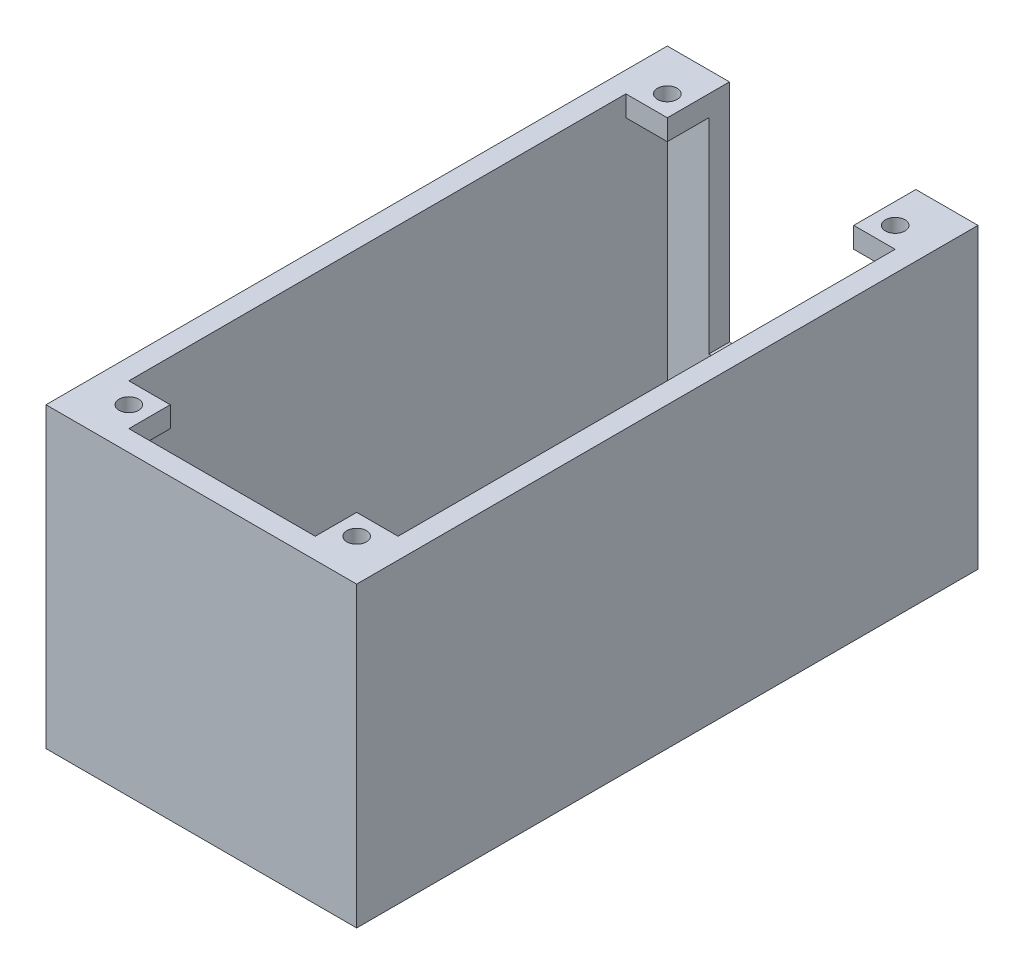
SolidWorks part; units mm, degrees
ref_plane "Front Plane" through (0, 0, 0) normal (0, 0, 1) x (1, 0, 0)
ref_plane "Top Plane" through (0, 0, 0) normal (0, 1, 0) x (1, 0, 0)
ref_plane "Right Plane" through (0, 0, 0) normal (1, 0, 0) x (0, 0, -1)
sketch "Sketch1" plane through (0, 0, 0) normal (0, 1, 0) x (1, 0, 0)
  line L1 (-19.05, -38.1) -> (19.05, -38.1)
  line L2 (-19.05, -38.1) -> (-19.05, 38.1)
  line L3 (-19.05, 38.1) -> (19.05, 38.1)
  line L4 (19.05, -38.1) -> (19.05, 38.1)
  line L5 (-19.05, -38.1) -> (19.05, 38.1) construction
  line L6 (-19.05, 38.1) -> (19.05, -38.1) construction
  point P0 (0, 0)
  dimension "D1" = 38.1
  dimension "D2" = 76.2
extrude "Boss-Extrude1" add sketch "Sketch1" along normal blind 2.54
hole_wizard "M2 Clearance Hole1 - to drone" positions "Sketch3" profile "Sketch4" hole size "M2" standard "ANSI Metric" end condition through all
sketch "Sketch3" plane through (0, 2.54, 0) normal (0, 1, 0) x (1, 0, 0)
  line L0 (-13.97, 0) -> (13.97, 0) construction
  point P0 (-13.97, 0)
  point P2 (13.97, 0)
  point P10 (0, 0)
  dimension "D1" = 27.94
sketch "Sketch4" plane through (-13.97, 2.54, 0) normal (1, 0, 0) x (0, 0, 1)
  line L0 (0, 0) -> (0, 2.54)
  line L1 (0, 2.54) -> (1.2, 2.54)
  line L2 (1.2, 2.54) -> (1.2, 0)
  line L5 (1.2, 0) -> (0, 0)
  line L11 (0, -6.35) -> (0, 107.95) construction
  dimension "Thru Hole Dia." = 2.4
  dimension "Thru Hole Depth" = 2.54
hole_wizard "M2 Clearance Hole2 - to Pi" positions "Sketch5" profile "Sketch6" hole size "M2" standard "ANSI Metric" end condition through all
sketch "Sketch5" plane through (0, 2.54, 0) normal (0, 1, 0) x (1, 0, 0)
  line L1 (-5.6998, -23.5001) -> (5.6998, -23.5001) construction
  line L2 (-5.6998, -23.5001) -> (-5.6998, 23.5001) construction
  line L3 (-5.6998, 23.5001) -> (5.6998, 23.5001) construction
  line L4 (5.6998, -23.5001) -> (5.6998, 23.5001) construction
  line L5 (-5.6998, -23.5001) -> (5.6998, 23.5001) construction
  line L6 (-5.6998, 23.5001) -> (5.6998, -23.5001) construction
  point P0 (-5.6998, 23.5001)
  point P2 (5.6998, 23.5001)
  point P4 (5.6998, -23.5001)
  point P6 (-5.6998, -23.5001)
  point P62 (0, 0)
  dimension "D1" = 11.3995
  dimension "D2" = 47.0002
sketch "Sketch6" plane through (-5.6998, 2.54, -23.5001) normal (1, 0, 0) x (0, 0, 1)
  line L0 (0, 0) -> (0, 2.54)
  line L1 (0, 2.54) -> (1.2, 2.54)
  line L2 (1.2, 2.54) -> (1.2, 0)
  line L5 (1.2, 0) -> (0, 0)
  line L11 (0, -6.35) -> (0, 107.95) construction
  dimension "Thru Hole Dia." = 2.4
  dimension "Thru Hole Depth" = 2.54
sketch "Sketch7" plane through (0, 2.54, 0) normal (0, 1, 0) x (1, 0, 0)
  line L0 (-19.05, -38.1) -> (-19.05, -35.56)
  line L1 (-19.05, 38.1) -> (-19.05, -38.1) construction
  line L2 (-16.51, -35.56) -> (16.51, -35.56)
  line L3 (19.05, -38.1) -> (19.05, 38.1) construction
  line L5 (19.05, -38.1) -> (-19.05, -38.1)
  line L6 (-16.51, -35.56) -> (-16.51, 38.1)
  line L7 (19.05, 38.1) -> (-19.05, 38.1) construction
  line L8 (-16.51, 38.1) -> (-19.05, 38.1)
  line L9 (-19.05, 38.1) -> (-19.05, -35.56)
  line L10 (19.05, -38.1) -> (19.05, 38.1)
  line L11 (19.05, 38.1) -> (16.51, 38.1)
  line L12 (16.51, 38.1) -> (16.51, -35.56)
  point P19 (-15.24, -35.0161)
  point P20 (0, 0)
  point P21 (17.78, -37.9711)
  dimension "D1" = 2.54
extrude "Boss-Extrude2" add sketch "Sketch7" along normal blind 33.9852
sketch "Sketch9" plane through (0, 0, -38.1) normal (0, 0, -1) x (-1, 0, 0)
  line L2 (-11.43, 8.89) -> (11.43, 8.89)
  line L3 (16.51, 36.5252) -> (16.51, 2.54) construction
  line L5 (16.51, 2.54) -> (-16.51, 2.54)
  line L6 (-10.3149, 8.89) -> (-10.3149, 2.54) construction
  line L7 (10.3149, 8.89) -> (10.3149, 2.54) construction
  line L8 (-10.3149, 5.715) -> (10.3149, 5.715) construction
  line L9 (11.43, 8.89) -> (11.43, 36.5252)
  line L10 (-16.51, 36.5252) -> (16.51, 36.5252) construction
  line L11 (11.43, 36.5252) -> (16.51, 36.5252)
  line L12 (16.51, 36.5252) -> (16.51, 2.54)
  line L13 (-16.51, 36.5252) -> (-11.43, 36.5252)
  line L14 (-11.43, 36.5252) -> (-11.43, 8.89)
  line L15 (-16.51, 36.5252) -> (-16.51, 2.54)
  circle A0 centre (-10.3149, 5.715) radius 1.5011
  circle A1 centre (10.3149, 5.715) radius 1.5011
  point P19 (0, 5.715)
  dimension "D1" = 3.0023
  dimension "D3" = 20.6299
  dimension "D2" = 6.35
  dimension "D4" = 5.08
extrude "Boss-Extrude4" add sketch "Sketch9" against normal blind 2.54 separate body
ref_plane "Plane1" through (0, 19.5326, 0) normal (0, 1, 0) x (1, 0, 0)
sketch "Sketch11" plane through (0, 19.5326, 0) normal (0, 1, 0) x (1, 0, 0)
  line L0 (-16.51, -35.56) -> (-16.51, -29.464)
  line L1 (-16.51, -35.56) -> (-16.51, 38.1) construction
  line L2 (-16.51, -29.464) -> (16.51, -29.464)
  line L3 (16.51, -29.464) -> (16.51, -35.56)
  line L4 (16.51, -35.56) -> (-16.51, -35.56) construction
  line L5 (16.51, -35.56) -> (-16.51, -35.56)
  line L6 (-6.985, -31.75) -> (6.985, -31.75) construction
  line L7 (0, -29.464) -> (0, -35.56) construction
  line L8 (16.51, 38.1) -> (16.51, -35.56) construction
  line L9 (-6.985, -30.734) -> (6.985, -30.734) construction
  circle A0 centre (-6.985, -31.75) radius 1.016
  circle A1 centre (6.985, -31.75) radius 1.016
  point P5 (-8.7307, -31.75)
  point P18 (0, -31.75)
  dimension "D1" = 2.032
  dimension "D2" = 3.81
  dimension "D3" = 13.97
  dimension "D4" = 1.27
extrude "Boss-Extrude6" add sketch "Sketch11" against normal blind 2.54
sketch "Sketch12" plane through (0, 36.5252, 0) normal (0, 1, 0) x (1, 0, 0)
  line L1 (16.51, 38.1) -> (16.51, -35.56) construction
  line L4 (-16.51, 33.02) -> (16.51, 33.02) construction
  line L7 (-16.51, -35.56) -> (-16.51, 38.1) construction
  line L10 (-16.51, -30.48) -> (-11.43, -30.48)
  line L12 (16.51, -35.56) -> (16.51, -30.48)
  line L15 (11.43, -30.48) -> (11.43, -35.56)
  line L16 (16.51, -35.56) -> (-16.51, -35.56) construction
  line L17 (11.43, -35.56) -> (16.51, -35.56)
  line L18 (-16.51, -35.56) -> (-11.43, -35.56)
  line L19 (-11.43, -35.56) -> (-11.43, -30.48)
  line L21 (-16.51, -30.48) -> (-16.51, -35.56)
  line L22 (16.51, -30.48) -> (11.43, -30.48)
  line L23 (16.51, 35.56) -> (11.43, 35.56)
  line L24 (11.43, 35.56) -> (11.43, 30.48)
  line L25 (11.43, 30.48) -> (16.51, 30.48)
  line L26 (16.51, 30.48) -> (16.51, 35.56)
  line L27 (-16.51, 35.56) -> (-11.43, 35.56)
  line L28 (-16.51, 35.56) -> (-11.43, 35.56) construction
  line L29 (-11.43, 35.56) -> (-11.43, 38.1) construction
  line L30 (-11.43, 35.56) -> (-11.43, 30.48)
  line L31 (-11.43, 30.48) -> (-16.51, 30.48)
  line L32 (-16.51, 30.48) -> (-16.51, 35.56)
  line L65 (13.97, 38.1) -> (13.97, -33.02)
  line L66 (-13.97, -33.02) -> (-13.97, 38.1)
  line L67 (13.97, -33.02) -> (-13.97, -33.02)
  line L68 (13.97, 38.1) -> (13.97, -33.02) construction
  line L69 (-13.97, -33.02) -> (-13.97, 38.1) construction
  line L70 (13.97, -33.02) -> (-13.97, -33.02) construction
  dimension "D2" = 2.54
  dimension "D3" = 2.54
  dimension "D1" = 2.54
extrude "Boss-Extrude7" add sketch "Sketch12" against normal blind 2.54
hole_wizard "M2 Clearance Hole1" positions "Sketch13" profile "Sketch14" hole size "M2" standard "ANSI Metric"
sketch "Sketch13" plane through (0, 36.5252, 0) normal (0, 1, 0) x (1, 0, 0)
  line L0 (-16.51, 33.02) -> (16.51, 33.02) construction
  line L1 (13.97, -33.02) -> (-13.97, -33.02) construction
  line L2 (-13.97, -33.02) -> (-13.97, 38.1) construction
  line L3 (13.97, 38.1) -> (13.97, -33.02) construction
  point P0 (-13.97, 33.02)
  point P4 (13.97, 33.02)
  point P6 (13.97, -33.02)
  point P10 (-13.97, -33.02)
  point P16 (0, 0)
  point P19 (0, 0)
sketch "Sketch14" plane through (-13.97, 36.5252, -33.02) normal (1, 0, 0) x (0, 0, 1)
  line L0 (0, 0) -> (0, 3.261)
  line L1 (0, 3.261) -> (1.2, 2.54)
  line L2 (1.2, 2.54) -> (1.2, 0)
  line L5 (1.2, 0) -> (0, 0)
  line L10 (0, 3.261) -> (-1.2, 2.54) construction
  line L11 (0, -6.35) -> (0, 107.95) construction
  dimension "Hole Dia." = 2.4
  dimension "Hole Depth" = 2.54
  dimension "Drill Angle" = 118
equation "\"D1@Sketch9\"=2*0.0591in"
equation "\"Wall_Thickness\"=0.1"
equation "\"D1@Boss-Extrude4\"=\"Wall_Thickness\""
